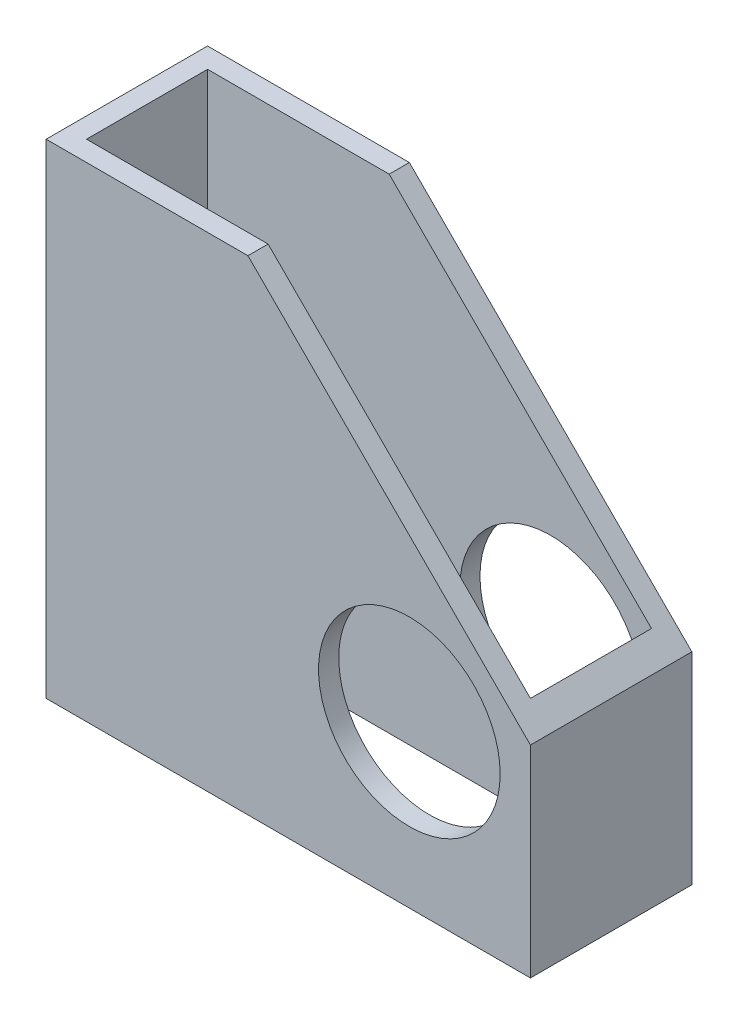
SolidWorks part; units mm, degrees
ref_plane "Front Plane" through (0, 0, 0) normal (0, 0, 1) x (1, 0, 0)
ref_plane "Top Plane" through (0, 0, 0) normal (0, 1, 0) x (1, 0, 0)
ref_plane "Right Plane" through (0, 0, 0) normal (1, 0, 0) x (0, 0, -1)
sketch "Sketch1" plane through (0, 0, 0) normal (0, 0, 1) x (1, 0, 0)
  line L1 (-38.1, 38.1) -> (38.1, 38.1)
  line L2 (-38.1, 38.1) -> (-38.1, -38.1)
  line L3 (-38.1, -38.1) -> (38.1, -38.1)
  line L4 (38.1, 38.1) -> (38.1, -38.1)
  line L5 (-38.1, 38.1) -> (38.1, -38.1) construction
  line L6 (-38.1, -38.1) -> (38.1, 38.1) construction
  circle A0 centre (19.05, -12.7) radius 14.2875
  point P0 (0, 0)
  dimension "D3" = 57.15
  dimension "D4" = 25.4
  dimension "D5" = 28.575
  dimension "D1" = 76.2
  dimension "D2" = 76.2
extrude "Boss-Extrude1" add sketch "Sketch1" along normal mid plane 25.4
hole_wizard "1/4 (0.25) Diameter Hole1" positions "Sketch5" profile "Sketch6" hole size "1/4" standard "ANSI Inch"
sketch "Sketch5" plane through (-38.1, 0, 0) normal (-1, 0, 0) x (0, 0, 1)
  line L0 (12.7, -38.1) -> (-12.7, -38.1) construction
  point P0 (0, -9.525)
  point P2 (0, -28.575)
  dimension "D1" = 9.525
  dimension "D2" = 19.05
sketch "Sketch6" plane through (-38.1, -9.525, 0) normal (0, 1, 0) x (0, 0, 1)
  line L0 (0, 0) -> (0, 6.9877)
  line L1 (0, 6.9877) -> (3.175, 5.08)
  line L2 (3.175, 5.08) -> (3.175, 0)
  line L5 (3.175, 0) -> (0, 0)
  line L10 (0, 6.9877) -> (-3.175, 5.08) construction
  line L11 (0, -6.35) -> (0, 107.95) construction
  dimension "Hole Dia." = 6.35
  dimension "Hole Depth" = 5.08
  dimension "Drill Angle" = 118
chamfer "Chamfer1" distance 44.45 angle 45 1 edges at (38.1, 38.1, 0)
sketch "Sketch7" plane through (0, -38.1, 0) normal (0, -1, 0) x (1, 0, 0)
  line L8 (-34.925, -9.525) -> (34.925, -9.525)
  line L9 (34.925, -9.525) -> (34.925, 9.525)
  line L10 (34.925, 9.525) -> (-34.925, 9.525)
  line L11 (-34.925, 9.525) -> (-34.925, -9.525)
  line L12 (-34.925, -9.525) -> (34.925, -9.525)
  line L13 (34.925, -9.525) -> (34.925, 9.525)
  line L14 (34.925, 9.525) -> (-34.925, 9.525)
  line L15 (-34.925, 9.525) -> (-34.925, -9.525)
  dimension "D1" = 3.175
extrude "Cut-Extrude1" cut sketch "Sketch7" against normal through all
